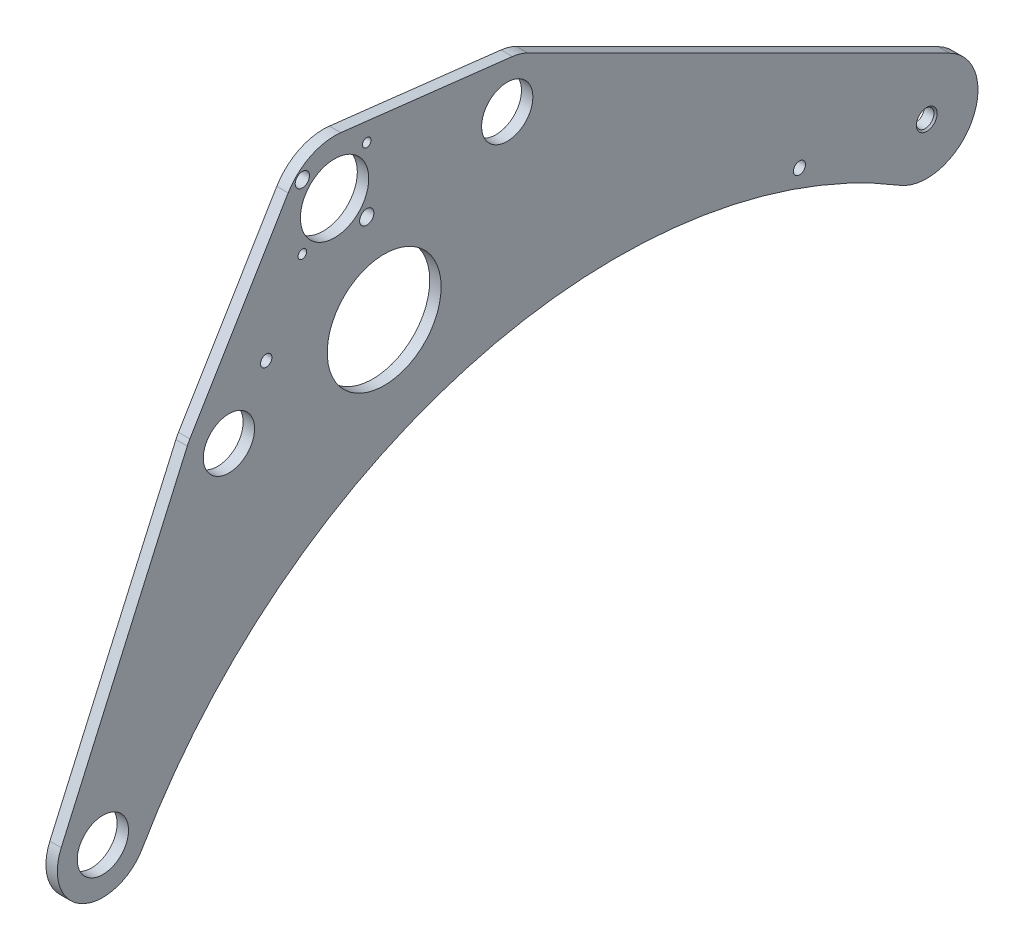
SolidWorks part; units mm, degrees
material "Acrylic (Medium-high impact)"
ref_plane "right palne" through (0, 0, 0) normal (0, 0, 1) x (1, 0, 0)
ref_plane "Top Plane" through (0, 0, 0) normal (0, 1, 0) x (1, 0, 0)
ref_plane "Right Plane" through (0, 0, 0) normal (1, 0, 0) x (0, 0, -1)
sketch "Sketch1" plane through (0, 0, 0) normal (1, 0, 0) x (0, 0, -1)
  line L0 (-548.7618, -304.8) -> (152.435, -304.8)
  line L1 (-192.8252, -101.6) -> (-152.4, -101.6)
  line L2 (-234.95, -143.7248) -> (-234.95, -186.4752)
  line L3 (-192.8252, -228.6) -> (-152.4, -228.6)
  line L4 (-152.4, -101.6) -> (-152.4, -228.6)
  line L5 (-328.8838, 146.9566) -> (-232.6048, 140.6066)
  line L6 (-219.3072, 106.9957) -> (-444.7644, -134.3043)
  line L7 (-477.6661, -112.5536) -> (-407.385, 46.1964)
  line L8 (-390.6035, 58.0432) -> (-367.7021, 59.773)
  line L10 (-476.25, -304.8) -> (-476.25, -143.7248)
  line L11 (314.7831, 139.7) -> (-192.8252, 139.7)
  line L12 (-133.3527, -63.5) -> (-641.3527, -63.5)
  line L16 (-360.4684, 66.396) -> (-349.9333, 130.2555)
  circle A1 centre (0, 0) radius 6.35
  circle A6 centre (-459.3781, -120.65) radius 9.525
  circle A7 centre (-389.0971, 38.1) radius 9.525
  circle A8 centre (-233.921, 120.65) radius 9.525
  arc A9 (-234.95, -186.4752) -> (-192.8252, -228.6) centre (-192.8252, -186.4752) ccw
  arc A10 (-192.8252, -101.6) -> (-234.95, -143.7248) centre (-192.8252, -143.7248) ccw
  circle A11 centre (-186.3309, 0) radius 120.65
  circle A12 centre (-330.2, 127) radius 29.845
  arc A19 (-349.9333, 130.2555) -> (-328.8838, 146.9566) centre (-330.2, 127) cw
  arc A20 (-232.6048, 140.6066) -> (-219.3072, 106.9957) centre (-233.921, 120.65) cw
  arc A21 (-444.7644, -134.3043) -> (-477.6661, -112.5536) centre (-459.3781, -120.65) cw
  arc A22 (-407.385, 46.1964) -> (-390.6035, 58.0432) centre (-389.0971, 38.1) cw
  arc A23 (-192.8252, 139.7) -> (-476.25, -143.7248) centre (-192.8252, -143.7248) ccw
  arc A28 (-367.7021, 59.773) -> (-360.4684, 66.396) centre (-368.3, 67.688) ccw
  point P23 (-346.32, 71.6886)
  point P24 (0, 0)
  point P25 (0, 0)
  point P26 (-325.8021, 72.5778)
  point P27 (-321.4825, 65.7282)
  point P42 (-304.1278, 39.7059)
  point P43 (-290.0189, -21.9684)
  point P44 (0, 0)
  point P47 (-290.1792, 59.4471)
  point P48 (-298.387, 45.8175)
  point P49 (-303.4177, 45.2022)
  point P50 (0, 0)
  point P51 (-360.6848, 68.7171)
  point P52 (-342.9863, -169.3522)
  point P53 (-362.1731, 73.7048)
  point P54 (-282.299, -18.6913)
  point P55 (-364.1085, 73.0943)
  point P56 (-186.3309, 0)
  point P57 (-370.3898, 67.0557)
  circle B0 centre (-389.0971, 38.1) radius 20
  line B1 (-459.3781, -120.65) -> (-445.4292, -105.3497)
  circle B2 centre (-459.3781, -120.65) radius 20
  circle B3 centre (-233.921, 120.65) radius 20
  line B4 (-330.2, 127) -> (-326.8662, 143.2097)
  circle B5 centre (-330.2, 127) radius 20
  circle B6 centre (-603.5064, -180.5864) radius 6.35
  circle B7 centre (-368.3, 67.688) radius 7.9375
  dimension "D1" = 12.7
  dimension "D2" = 19.05
  dimension "D3" = 42.1248
  dimension "D4" = 127
  dimension "D7" = 203.2
  dimension "D6" = 241.3
  dimension "D16" = 59.69
  dimension "D10" = 25.4
  dimension "D11" = 25.4
  dimension "D12" = 25.4
  dimension "D5" = 82.55
  dimension "D8" = 304.8
  dimension "D9" = 152.4
  dimension "D13" = 57.15
  dimension "D14" = 101.6
  dimension "D15" = 184.15
  dimension "D23" = 241.3
  dimension "D24" = 241.3
  dimension "D25" = 241.3
  dimension "D26" = 508
  dimension "D21" = 330.2
  dimension "D22" = 127
  dimension "D20" = 368.3
sketch_block_instance "Block1-1"
sketch_block "Block1" parameters "D1"=8
sketch_block_instance "Block2-1"
sketch_block "Block2" parameters "D1"=8
sketch_block_instance "Block3-1"
sketch_block "Block3" parameters "D1"=8
sketch_block_instance "Block4-1"
sketch_block "Block4" parameters "D1"=40, "D2"=8
sketch_block_instance "Block5-1"
sketch_block "Block5" parameters "D1"=8
sketch_block_instance "Block6-1"
sketch_block "Block6" parameters "D1"=15.875
other "Belt2"
sketch "Sketch10" plane through (0, 0, 0) normal (-1, 0, 0) x (0, 0, 1)
  line L0 (0, 0) -> (459.3781, -120.65)
  line L1 (0, 0) -> (122.9281, 458.7738)
  line L2 (0, 0) -> (71.0041, 12.0594)
  line L4 (0, 0) -> (-11.707, 71.0631)
  line L6 (-11.707, 71.0631) -> (16.9816, 63.376)
  line L7 (71.0041, 12.0594) -> (63.4595, -16.6669)
  line L8 (71.0041, 12.0594) -> (-215.9, 216.7284)
  line L9 (-215.9, 216.7284) -> (-11.707, 71.0631)
  line L10 (0, 0) -> (745.3451, 0) construction
  dimension "D1" = 250.825
  dimension "D2" = 352.425
  dimension "D3" = 75
  dimension "D4" = 14.716
  dimension "D5" = 215.9
sketch "Sketch2" plane through (0, 0, 0) normal (1, 0, 0) x (0, 0, -1)
  line L1 (-482.6038, -110.3676) -> (-412.3228, 48.3824)
  line L3 (-410.8771, 51.1687) -> (-356.0637, 142.5191)
  line L6 (-1064.3654, -146.05) -> (154.0419, -146.05) construction
  line L7 (-1029.8132, 157.1625) -> (188.5941, 157.1625) construction
  line L11 (-326.7318, 156.9624) -> (-231.0004, 145.8815)
  line L13 (12.7913, 25.5522) -> (-222.551, 143.3631)
  arc A0 (-410.8771, 51.1687) -> (-412.3228, 48.3824) centre (-389.0971, 38.1) ccw
  arc A2 (-482.6038, -110.3676) -> (-437.3473, -133.2913) centre (-459.3781, -120.65) ccw
  arc A4 (-326.7318, 156.9624) -> (-356.0637, 142.5191) centre (-330.2, 127) ccw
  arc A5 (-14.8266, -24.4275) -> (12.7913, 25.5522) centre (0, 0) ccw
  arc A8 (-437.3473, -133.2913) -> (-103.9177, 11.8862) centre (-172.9775, -284.9872) cw
  circle A12 centre (-459.3781, -120.65) radius 9.525 construction
  circle A13 centre (-389.0971, 38.1) radius 9.525 construction
  circle A17 centre (-71.0041, 12.0594) radius 3.3782
  arc A21 (-103.9177, 11.8862) -> (-14.8266, -24.4275) centre (-172.9775, -284.9872) cw
  arc A22 (-222.551, 143.3631) -> (-231.0004, 145.8815) centre (-233.921, 120.65) ccw
  point P20 (-232.0008, 151.0127)
  dimension "D1" = 25.4
  dimension "D2" = 57.15
  dimension "D3" = 60.325
  dimension "D4" = 304.8
  dimension "D7" = 6.7564
  dimension "D5" = 25.4
extrude "Boss-Extrude1" add sketch "Sketch2" along normal blind 6.35
sketch "Sketch3" plane through (6.35, 0, 0) normal (1, 0, 0) x (0, 0, -1)
  line L0 (-312.2395, 144.9605) -> (-348.1605, 109.0395) construction
  line L1 (-330.2, 127) -> (-330.2, 205.0182) construction
  line L2 (-348.1605, 144.9605) -> (-312.2395, 109.0395) construction
  circle A0 centre (-233.921, 120.65) radius 14.2875
  circle A1 centre (-389.0971, 38.1) radius 14.2875
  circle A2 centre (-459.3781, -120.65) radius 14.2875
  circle A3 centre (-330.2, 127) radius 19.05
  circle A5 centre (-348.1605, 109.0395) radius 2.413
  circle A7 centre (-312.2395, 109.0395) radius 3.9687
  circle A8 centre (-312.2395, 144.9605) radius 2.413
  circle A9 centre (-348.1605, 144.9605) radius 3.9687
  circle A10 centre (-368.3, 67.688) radius 3.175
  point P18 (-330.2, 127)
  point P28 (-330.2, 127)
  dimension "D1" = 38.1
  dimension "D2" = 28.575
  dimension "D3" = 4.826
  dimension "D4" = 50.8
  dimension "D5" = 45
  dimension "D6" = 7.9375
  dimension "D7" = 50.8
  dimension "D8" = 6.35
  dimension "D9" = 28.575
extrude "Cut-Extrude1" cut sketch "Sketch3" against normal up to next
hole_wizard "3/8 Clearance Hole2" positions "Sketch7" profile "Sketch8" hole size "3/8" standard "ANSI Inch" end condition through all
sketch "Sketch7" plane through (6.35, 0, 0) normal (1, 0, 0) x (0, 0, -1)
  point P0 (0, 0)
sketch "Sketch8" plane through (6.35, 0, 0) normal (0, 1, 0) x (0, 0, -1)
  line L0 (0, 0) -> (0, 6.35)
  line L1 (0, 6.35) -> (4.9022, 6.35)
  line L2 (4.9022, 6.35) -> (4.9022, 0.8915)
  line L3 (4.9022, 0.8915) -> (5.7937, 0)
  line L5 (5.7937, 0) -> (0, 0)
  line L6 (-4.9022, 0.8915) -> (-5.7937, 0) construction
  line L11 (0, -6.35) -> (0, 107.95) construction
  dimension "Thru Hole Dia." = 9.8044
  dimension "Thru Hole Depth" = 6.35
  dimension "Near C'Sink Dia." = 11.5875
  dimension "Near C'Sink Angle" = 90
sketch "Sketch9" plane through (6.35, 0, 0) normal (1, 0, 0) x (0, 0, -1)
  line L0 (-495.9857, -146.05) -> (27.4607, -146.05) construction
  line L1 (100.4878, 157.1625) -> (-422.9585, 157.1625) construction
  arc A0 (-326.7318, 156.9624) -> (-356.0637, 142.5191) centre (-330.2, 127) ccw construction
  arc A1 (-482.6038, -110.3676) -> (-437.3473, -133.2913) centre (-459.3781, -120.65) ccw construction
  dimension "D1" = 303.2125
sketch "Sketch11" plane through (6.35, 0, 0) normal (1, 0, 0) x (0, 0, -1)
  line L0 (-323.4079, 109.202) -> (-281.6508, -0.2186) construction
  circle A0 centre (-302.5294, 54.4917) radius 31.75
  circle A1 centre (-330.2, 127) radius 19.05 construction
  arc A2 (-14.8266, -24.4275) -> (-437.3473, -133.2913) centre (-172.9775, -284.9872) ccw construction
  point P6 (-172.9775, -284.9872)
  dimension "D1" = 63.5
extrude "Cut-Extrude2" cut sketch "Sketch11" against normal through all
